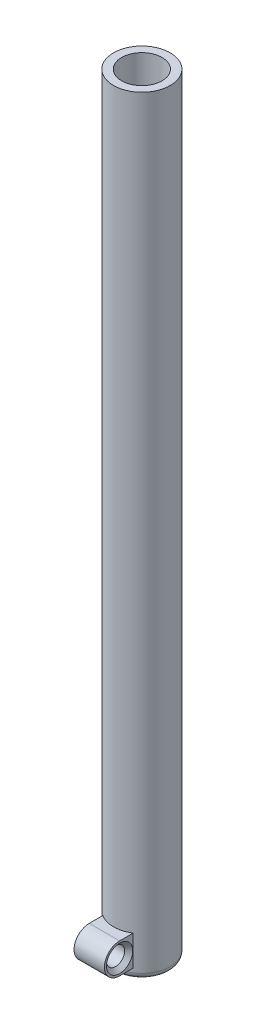
SolidWorks part; units mm, degrees
material "PE Niska/średnia gęstość"
ref_plane "Płaszczyzna przednia" through (0, 0, 0) normal (0, 0, 1) x (1, 0, 0)
ref_plane "Płaszczyzna górna" through (0, 0, 0) normal (0, 1, 0) x (1, 0, 0)
ref_plane "Płaszczyzna prawa" through (0, 0, 0) normal (1, 0, 0) x (0, 0, -1)
sketch "Szkic1" plane through (0, 0, 0) normal (0, 1, 0) x (1, 0, 0)
  circle A0 centre (0, 0) radius 14
  circle A1 centre (0, 0) radius 10
  dimension "D1" = 28
  dimension "D2" = 20
extrude "Dodanie-wyciągnięcie1" add sketch "Szkic1" along normal blind 380
ref_plane "Płaszczyzna1" through (0, 0, 14) normal (0, 0, 1) x (1, 0, 0)
sketch "Szkic2" plane through (0, 0, 14) normal (0, 0, 1) x (1, 0, 0)
  line L1 (-7.5, 20) -> (7.5, 20)
  line L2 (-7.5, 20) -> (-7.5, 5)
  line L3 (-7.5, 5) -> (7.5, 5)
  line L4 (7.5, 20) -> (7.5, 5)
  line L5 (-14, 0) -> (14, 0) construction
  point P5 (0, 5)
  dimension "D1" = 15
  dimension "D2" = 15
  dimension "D3" = 5
extrude "Dodanie-wyciągnięcie2" add sketch "Szkic2" along normal blind 12 and the other way up to surface other way up to face at (0, 380, 14)
fillet "Zaokrąglenie1" 2 edges at (0, 20, 26) (0, 5, 26) type full round first side face at (0, 20, 19.4554) second side face at (0, 5, 19.4554) middle face at (0, 12.5, 26)
sketch "Szkic3" plane through (7.5, 0, 0) normal (1, 0, 0) x (0, 0, -1)
  circle A0 centre (-18.5, 12.5) radius 4.5
  dimension "D1" = 9
extrude "Wytnij-wyciągnięcie1" cut sketch "Szkic3" against normal through all
chamfer "Sfazowanie2" distance 2 angle 45 2 edges at (-7.5, 17, 18.5) (7.5, 17, 18.5)
fillet "Zaokrąglenie2" radius 3 1 edges at (0, 0, 14)
ref_plane "Płaszczyzna2" through (0, 0, 18.5) normal (0, 0, 1) x (1, 0, 0)
sketch "Szkic4" plane through (0, 0, 18.5) normal (0, 0, 1) x (1, 0, 0)
  line L0 (0, 380) -> (0, 3) construction
  line L1 (-5.5, 12.5) -> (5.5, 12.5) construction
  point P0 (0, 12.5)
